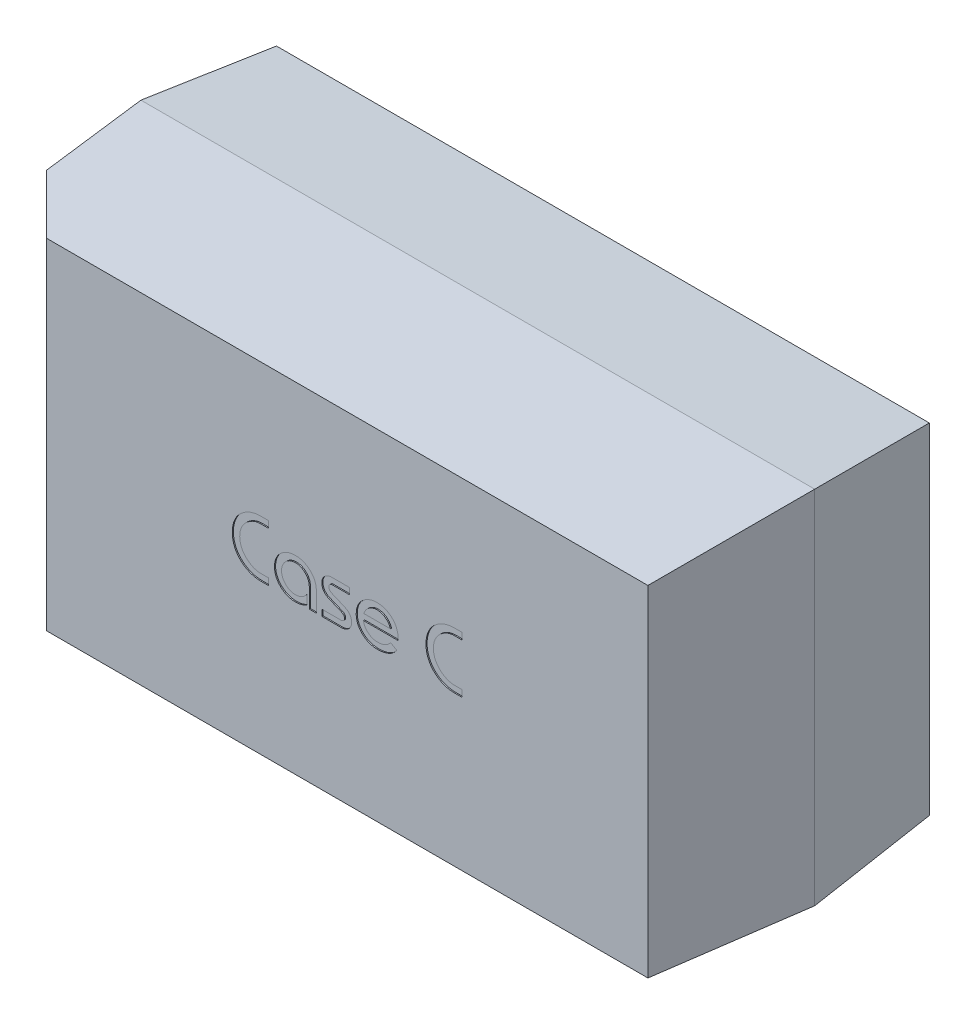
SolidWorks part; units mm, degrees
ref_plane "Front Plane" through (0, 0, 0) normal (0, 0, 1) x (1, 0, 0)
ref_plane "Top Plane" through (0, 0, 0) normal (0, 1, 0) x (1, 0, 0)
ref_plane "Right Plane" through (0, 0, 0) normal (1, 0, 0) x (0, 0, -1)
sketch "Sketch1" plane through (0, 0, 0) normal (0, 0, 1) x (1, 0, 0)
  line L1 (0, 0) -> (6, 0)
  line L2 (0, 0) -> (0, 3.22)
  line L3 (0, 3.22) -> (6, 3.22)
  line L4 (6, 0) -> (6, 3.22)
  dimension "D1" = 6
  dimension "D2" = 3.22
extrude "Boss-Extrude1" add sketch "Sketch1" along normal blind 2.5
chamfer "Chamfer3" distance 1.5 distance2 0.1 4 edges at (6, 1.61, 2.5) (3, 0, 2.5) (0, 1.61, 2.5) (3, 3.22, 2.5) first distance on face at (6, 1.61, 1.25) first distance on face at (3, 0, 1.25) first distance on face at (0, 1.61, 1.25) first distance on face at (3, 3.22, 1.25)
chamfer "Chamfer4" distance 0.1 distance2 1.2 4 edges at (3, 3.22, 0) (0, 1.61, 0) (3, 0, 0) (6, 1.61, 0) first distance on face at (3, 1.61, 0)
sketch "Sketch2" plane through (0, 0, 0) normal (0, 0, -1) x (-1, 0, 0)
  line L1 (-1.5, 3.02) -> (-4.5, 3.02)
  line L2 (-1.5, 3.02) -> (-1.5, 0.2)
  line L3 (-1.5, 0.2) -> (-4.5, 0.2)
  line L4 (-4.5, 3.02) -> (-4.5, 0.2)
  line L8 (-5.9, 0.1) -> (-0.1, 0.1) construction
  line L9 (-0.1, 3.12) -> (-5.9, 3.12) construction
  line L10 (-3, 0.1) -> (-3, 3.12) construction
  line L11 (-0.1, 0.1) -> (-0.1, 3.12) construction
  line L12 (-5.9, 3.12) -> (-5.9, 0.1) construction
  dimension "D1" = 0.1
  dimension "D2" = 0.1
  dimension "D3" = 1.4
  dimension "D4" = 1.4
extrude "Boss-Extrude2" add sketch "Sketch2" along normal blind 0.1
chamfer "Chamfer5" distance 0.1 angle 30 2 edges at (4.5, 1.61, -0.1) (1.5, 1.61, -0.1) first distance on face at (4.5, 1.61, -0.05) first distance on face at (1.5, 1.61, -0.05)
sketch "Sketch5" plane through (0, 0, 2.5) normal (0, 0, 1) x (1, 0, 0)
  text T0 "Case C" font "Belgium" height 0.5
extrude "Cut-Extrude2" cut sketch "Sketch5" against normal blind 0.01
sketch "Sketch7" plane through (0, 0, 0) normal (0, 1, 0) x (1, 0, 0)
  line L0 (0.5658, -2.5068) -> (0.0658, -2.0068)
  line L1 (0.0658, -2.0068) -> (0.0658, -2.5068)
  line L2 (0.0658, -2.5068) -> (0.5658, -2.5068)
  dimension "D1" = 0.5
  dimension "D2" = 0.5
extrude "Cut-Extrude4" cut sketch "Sketch7" along normal blind 10
